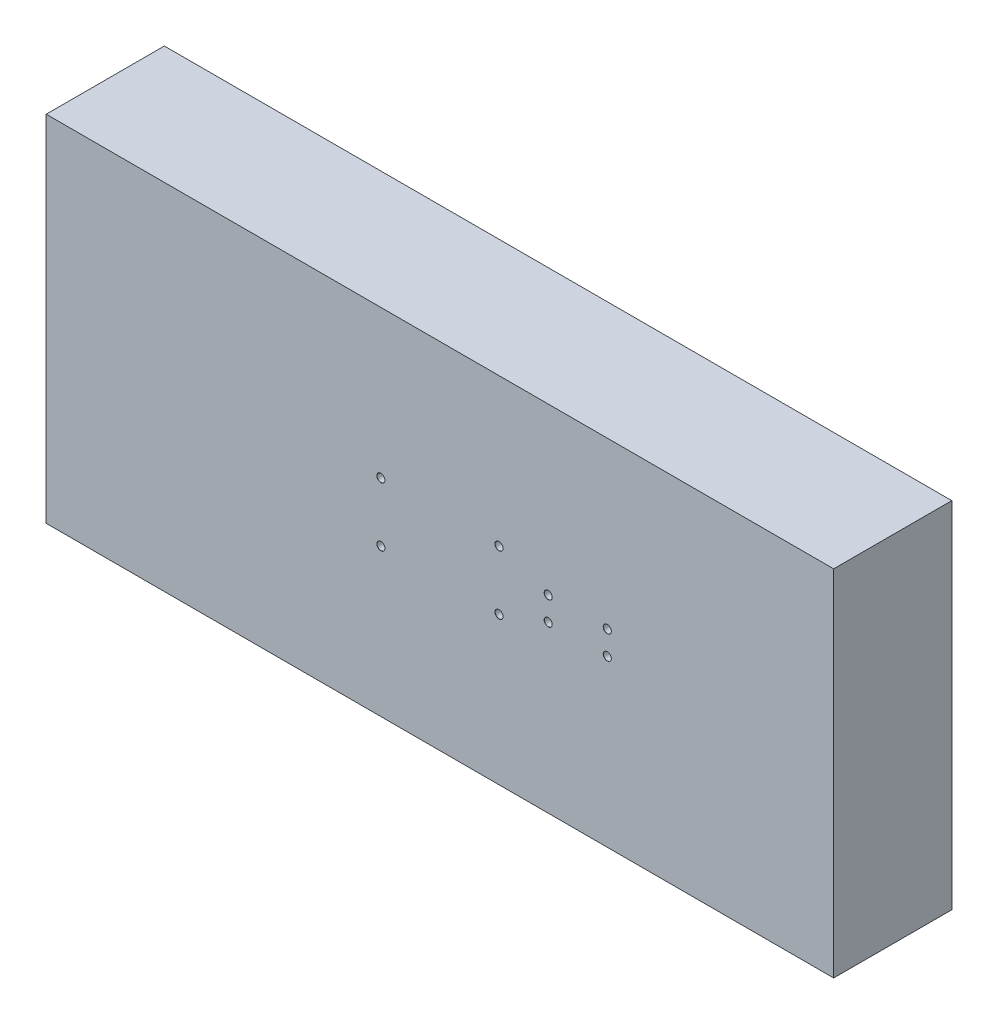
SolidWorks part; units mm, degrees
material "Cast Alloy Steel"
ref_plane "Front Plane" through (0, 0, 0) normal (1, 0, 0) x (0, 1, 0)
ref_plane "Top Plane" through (0, 0, 0) normal (0, 0, 1) x (0, 1, 0)
ref_plane "Right Plane" through (0, 0, 0) normal (0, 1, 0) x (-1, 0, 0)
sketch "Sketch1" plane through (0, 0, 0) normal (1, 0, 0) x (0, 1, 0)
  line L1 (0, -55) -> (0, 55) construction
  line L2 (-90, 30) -> (0, 30)
  line L3 (-90, 30) -> (-90, 0)
  line L4 (-90, 0) -> (0, 0)
  line L5 (0, 30) -> (0, 0)
  line L6 (0, 30) -> (150, 30)
  line L7 (0, 30) -> (0, 1030)
  line L8 (0, 1030) -> (150, 1030)
  line L9 (150, 30) -> (150, 1030)
  line L10 (-90, 0) -> (-240, 0)
  line L11 (-90, 0) -> (-90, -500)
  line L12 (-90, -500) -> (-240, -500)
  line L13 (-240, 0) -> (-240, -500)
  line L14 (55, 0) -> (-55, 0) construction
  dimension "D1" = 1000
  dimension "D2" = 150
  dimension "D3" = 150
  dimension "D4" = 30
  dimension "D5" = 90
  dimension "D6" = 500
  dimension "D7" = 0
  dimension "D8" = 0
extrude "Boss-Extrude2" add sketch "Sketch1" along normal blind 100 and the other way blind 100 contours L5 L2 L3 L4 region at (0, -45, 15)
sketch "Sketch2" plane through (0, 0, 30) normal (0, 0, 1) x (1, 0, 0)
  line L1 (-15, -37.5) -> (15, -37.5)
  line L2 (-15, -37.5) -> (-15, -52.5)
  line L3 (-15, -52.5) -> (15, -52.5)
  line L4 (-100, -90) -> (100, -90)
  line L5 (100, -90) -> (100, 0)
  line L6 (100, 0) -> (-100, 0)
  line L7 (-100, 0) -> (-100, -90)
  line L8 (-100, -90) -> (100, -90)
  line L9 (100, -90) -> (100, 0)
  line L10 (100, 0) -> (-100, 0)
  line L11 (-100, 0) -> (-100, -90)
  line L12 (15, -37.5) -> (15, -52.5)
  point P8 (0, -37.5)
  point P10 (-15, -45)
  point P11 (-100, -45)
  point P13 (-15, -37.5)
  point P14 (-15, -52.5)
  point P15 (15, -37.5)
  point P16 (15, -52.5)
  dimension "D2" = 0
  dimension "D3" = 0
  dimension "D4" = 15
  dimension "D5" = 30
  dimension "D1" = 0
hole_wizard "Ø2.0mm Dowel Hole1" positions "Sketch2" profile "Sketch3" hole size "Ø2.0" standard "IS"
sketch "Sketch3" plane through (15, -52.5, 30) normal (1, 0, 0) x (0, -1, 0)
  line L0 (0, 0) -> (0, 10.6009)
  line L1 (0, 10.6009) -> (1, 10)
  line L2 (1, 10) -> (1, 0.025)
  line L3 (1, 0.025) -> (1.025, 0)
  line L5 (1.025, 0) -> (0, 0)
  line L6 (-1, 0.025) -> (-1.025, 0) construction
  line L10 (0, 10.6009) -> (-1, 10) construction
  line L11 (0, -6.35) -> (0, 107.95) construction
  dimension "Hole Dia." = 2
  dimension "Hole Depth" = 10
  dimension "Near C'Sink Dia." = 2.05
  dimension "Near C'Sink Angle" = 90
  dimension "Drill Angle" = 118
sketch "Sketch4" plane through (0, 0, 30) normal (0, 0, 1) x (1, 0, 0)
  line L1 (27.5, -42) -> (42.5, -42)
  line L2 (27.5, -42) -> (27.5, -48)
  line L3 (27.5, -48) -> (42.5, -48)
  line L4 (42.5, -42) -> (42.5, -48)
  line L8 (-100, -90) -> (100, -90)
  line L9 (100, -90) -> (100, 0)
  line L10 (100, 0) -> (-100, 0)
  line L11 (-100, 0) -> (-100, -90)
  line L12 (-100, -90) -> (100, -90)
  line L13 (100, -90) -> (100, 0)
  line L14 (100, 0) -> (-100, 0)
  line L15 (-100, 0) -> (-100, -90)
  point P6 (-100, -45)
  point P8 (27.5, -45)
  point P11 (27.5, -42)
  point P13 (27.5, -48)
  point P14 (42.5, -48)
  point P15 (42.5, -42)
  point P89 (35, -42)
  dimension "D2" = 0
  dimension "D3" = 15
  dimension "D4" = 6
  dimension "D5" = 35
  dimension "D1" = 0
hole_wizard "Ø2.0mm Dowel Hole2" positions "Sketch4" profile "Sketch5" hole size "Ø2.0" standard "IS"
sketch "Sketch5" plane through (42.5, -42, 30) normal (1, 0, 0) x (0, -1, 0)
  line L0 (0, 0) -> (0, 10.6009)
  line L1 (0, 10.6009) -> (1, 10)
  line L2 (1, 10) -> (1, 0.025)
  line L3 (1, 0.025) -> (1.025, 0)
  line L5 (1.025, 0) -> (0, 0)
  line L6 (-1, 0.025) -> (-1.025, 0) construction
  line L10 (0, 10.6009) -> (-1, 10) construction
  line L11 (0, -6.35) -> (0, 107.95) construction
  dimension "Hole Dia." = 2
  dimension "Hole Depth" = 10
  dimension "Near C'Sink Dia." = 2.05
  dimension "Near C'Sink Angle" = 90
  dimension "Drill Angle" = 118
